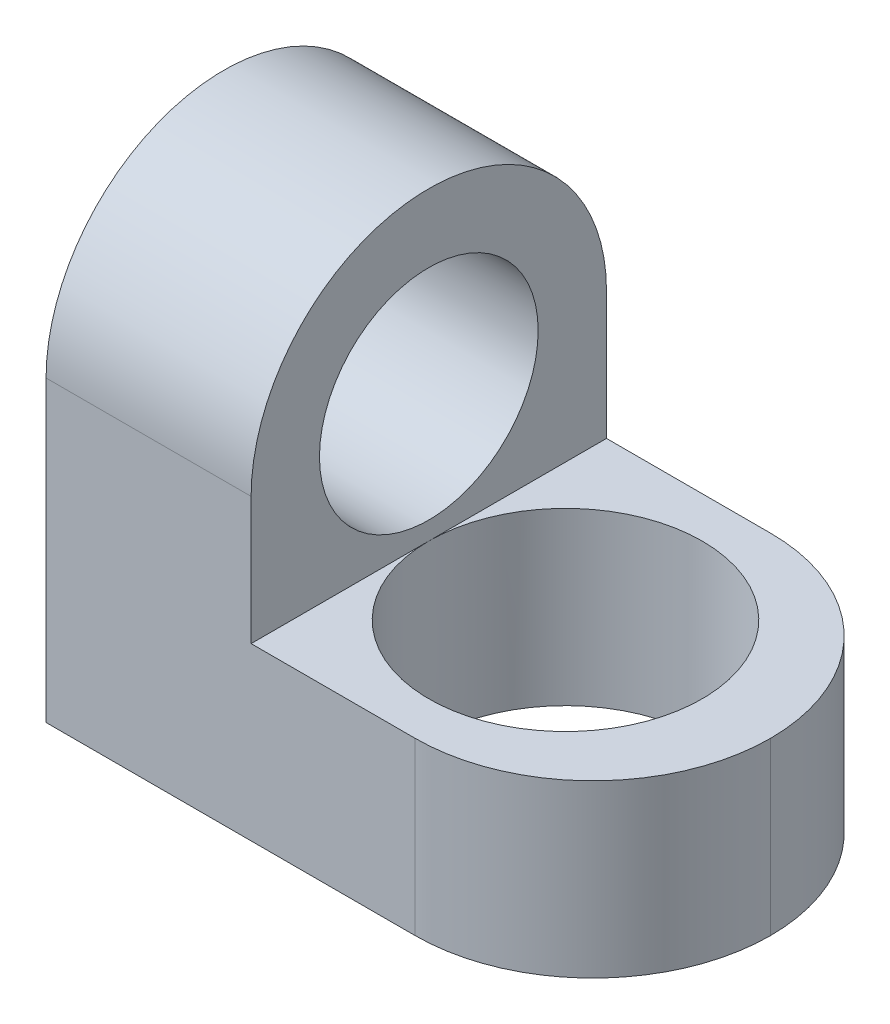
SolidWorks part; units mm, degrees
ref_plane "Front Plane" through (0, 0, 0) normal (0, 0, 1) x (1, 0, 0)
ref_plane "Top Plane" through (0, 0, 0) normal (0, 1, 0) x (1, 0, 0)
ref_plane "Right Plane" through (0, 0, 0) normal (1, 0, 0) x (0, 0, -1)
sketch "Sketch1" plane through (0, 0, 0) normal (1, 0, 0) x (0, 0, -1)
  line L2 (-2.6, 0) -> (-2.6, -4.3657)
  line L3 (-2.6, -4.3657) -> (2.6, -4.3657)
  line L4 (2.6, 0.6343) -> (2.6, -4.3657)
  circle A0 centre (0, 0) radius 1.6
  arc A1 (2.6, 0) -> (-2.6, 0) centre (0, 0) ccw
  dimension "D1" = 3.2
  dimension "D2" = 5.2
  dimension "D3" = 5
  dimension "D4" = 5.2
extrude "Boss-Extrude1" add sketch "Sketch1" along normal blind 3 contours L4 A1 L2 L3 A0 region at (0, 2.5131, 0)
sketch "Sketch2" plane through (3, 0, 0) normal (1, 0, 0) x (0, 0, -1)
  line L0 (2.6, 0) -> (2.6, -4.3657) construction
  line L1 (-2.6, -4.3657) -> (2.6, -4.3657)
  line L2 (-2.6, -4.3657) -> (-2.6, -1.8657)
  line L3 (-2.6, -1.8657) -> (2.6, -1.8657)
  line L4 (2.6, -4.3657) -> (2.6, -1.8657)
  dimension "D1" = 2.5
extrude "Boss-Extrude2" add sketch "Sketch2" along normal blind 5
fillet "Fillet1" radius 2.6 2 edges at (8, -3.1157, -2.6) (8, -3.1157, 2.6)
sketch "Sketch3" plane through (0, -4.3657, 0) normal (0, -1, 0) x (1, 0, 0)
  line L0 (8, 0) -> (0, 0) construction
  line L1 (0, 2.6) -> (0, -2.6) construction
  circle A0 centre (5, 0) radius 2
  dimension "D1" = 4
  dimension "D2" = 5
extrude "Cut-Extrude1" cut sketch "Sketch3" against normal blind 5
